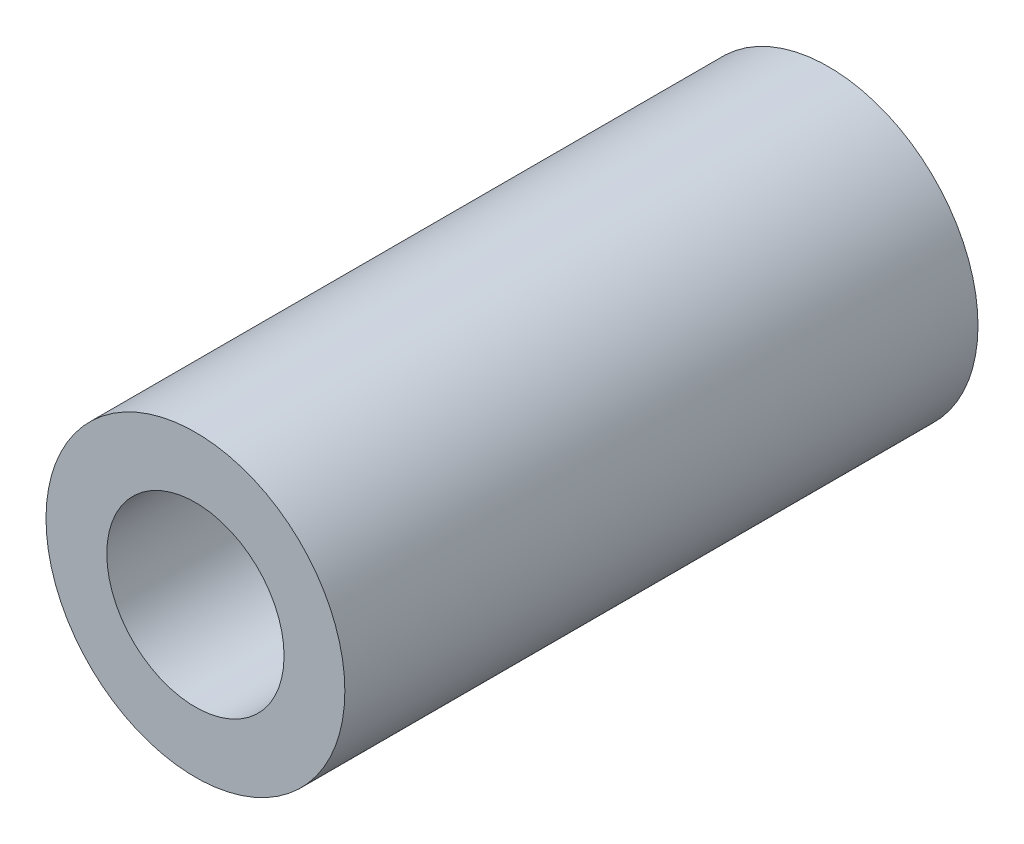
SolidWorks part; units mm, degrees
material "Copper"
ref_plane "Front Plane" through (0, 0, 0) normal (0, 0, 1) x (1, 0, 0)
ref_plane "Top Plane" through (0, 0, 0) normal (0, 1, 0) x (1, 0, 0)
ref_plane "Right Plane" through (0, 0, 0) normal (1, 0, 0) x (0, 0, -1)
sketch "Sketch1" plane through (0, 0, 0) normal (0, 0, 1) x (1, 0, 0)
  circle A0 centre (0, 0) radius 7
  circle A1 centre (0, 0) radius 11.8
  dimension "D1" = 14
  dimension "D2" = 23.6
extrude "Boss-Extrude1" add sketch "Sketch1" along normal blind 50
